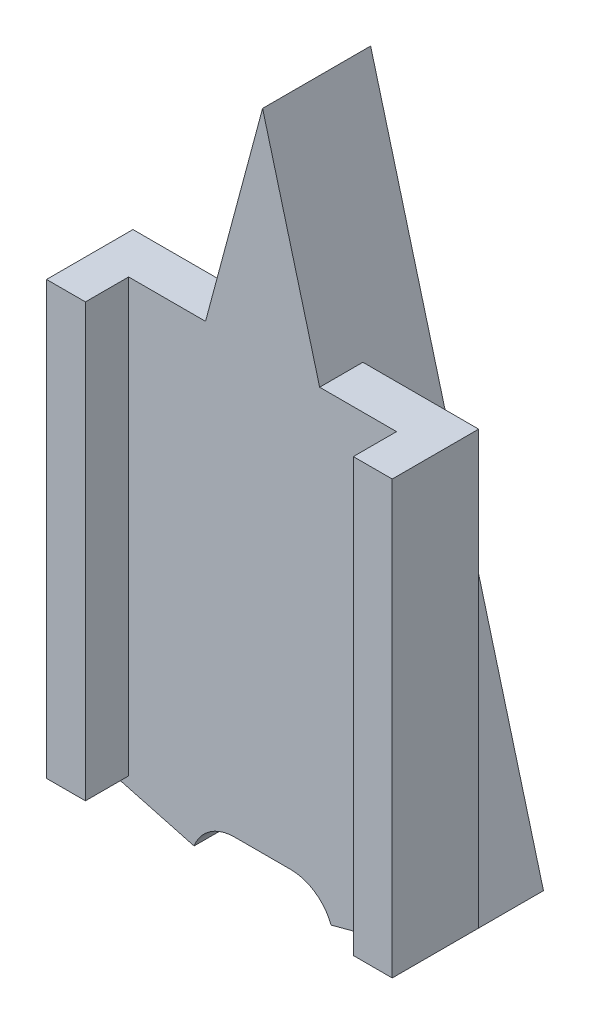
SolidWorks part; units mm, degrees
material "PA Type 6"
ref_plane "Ebene vorne" through (0, 0, 0) normal (0, 0, 1) x (1, 0, 0)
ref_plane "Ebene oben" through (0, 0, 0) normal (0, 1, 0) x (1, 0, 0)
ref_plane "Ebene rechts" through (0, 0, 0) normal (1, 0, 0) x (0, 0, -1)
sketch "Sketch1" plane through (0, 0, 0) normal (0, 0, 1) x (1, 0, 0)
  line L1 (0, 0) -> (8, 0)
  line L2 (0, 0) -> (0, -10)
  line L3 (0, -10) -> (8, -10)
  line L4 (8, 0) -> (8, -10)
extrude "Boss-Extrude1" add sketch "Sketch1" along normal blind 2
sketch "Sketch2" plane through (0, 0, 2) normal (0, 0, 1) x (1, 0, 0)
  line L0 (8, 0) -> (0, 0) construction
  line L1 (0.9, 0) -> (7.1, 0)
  line L2 (0.9, 0) -> (0.9, -10)
  line L3 (0.9, -10) -> (7.1, -10)
  line L4 (7.1, 0) -> (7.1, -10)
  line L5 (0, -10) -> (8, -10) construction
  line L6 (0, 0) -> (0, -10) construction
  line L7 (8, -10) -> (8, 0) construction
  dimension "D1" = 0.9
  dimension "D2" = 0.9
  dimension "D3" = 6.2
extrude "Cut-Extrude1" cut sketch "Sketch2" against normal blind 1
sketch "Sketch3" plane through (0, 0, 0) normal (0, 0, -1) x (-1, 0, 0)
  line L0 (-8, -10) -> (-4, 4.9282)
  line L1 (-8, -10) -> (-5.5852, -10.647)
  line L4 (-4, 0) -> (-4, -10) construction
  line L5 (-8, 0) -> (0, 0) construction
  line L6 (0, -10) -> (-8, -10) construction
  line L7 (-8, -5) -> (0, -5) construction
  line L8 (-8, -10) -> (-8, 0) construction
  line L9 (0, 0) -> (0, -10) construction
  line L10 (0, -10) -> (-4, 4.9282)
  line L11 (-4, -4.7311) -> (-5.5852, -10.647)
  line L12 (0, -10) -> (-2.4148, -10.647)
  line L13 (-2.4148, -10.647) -> (-4, -4.7311)
  dimension "D1" = 2.5
  dimension "D2" = 2.5
  dimension "D3" = 30
extrude "Boss-Extrude2" add sketch "Sketch3" along normal blind 1.5 and the other way blind 1
hole_wizard "M1x0.2 Tapped Hole1" positions "Sketch5" profile "Sketch4" tap size "M1x0.2" standard "DIN"
sketch "Sketch5" plane through (-2.5, -9.3301, 0) normal (-0.2588, -0.9659, 0) x (-0.9659, 0.2588, 0)
  line L0 (-3.8382, 1.5) -> (-3.8382, -1) construction
  line L1 (-5.0882, 1.5) -> (-2.5882, 1.5) construction
  line L2 (-5.0882, -1) -> (-2.5882, -1) construction
  line L4 (-5.0882, 0.25) -> (-2.5882, 0.25) construction
  line L5 (-5.0882, -1) -> (-5.0882, 1.5) construction
  line L6 (-2.5882, 0) -> (-2.5882, 1.5) construction
  point P0 (-5.116, 0.25)
sketch "Sketch4" plane through (2.4417, -10.6542, -0.25) normal (0, 0, 1) x (0.9659, -0.2588, 0)
  line L0 (0, 0) -> (0, 2.8403)
  line L1 (0, 2.8403) -> (0.4, 2.6)
  line L2 (0.4, 2.6) -> (0.4, 2)
  line L3 (0.4, 2) -> (0.5, 2)
  line L4 (0.5, 2) -> (0.5, 0)
  line L5 (0.5, 0) -> (0, 0)
  line L10 (0, 2.8403) -> (-0.4, 2.6) construction
  line L11 (0, -6.35) -> (0, 107.95) construction
  dimension "Tap Drill Dia." = 0.8
  dimension "Tap Drill Depth" = 2.6
  dimension "Thread Major Dia." = 1
  dimension "Thread Depth" = 2
  dimension "Drill Angle" = 118
hole_wizard "M1 Clearance Hole1" positions "Sketch6" profile "Sketch7" hole size "M1" standard "DIN"
sketch "Sketch6" plane through (3.0359, -11.3301, 0) normal (0.2588, -0.9659, 0) x (-0.9659, -0.2588, 0)
  point P0 (-2.3142, 0.25)
sketch "Sketch7" plane through (5.2712, -10.7312, -0.25) normal (0, 0, 1) x (0.9659, 0.2588, 0)
  line L0 (0, 0) -> (0, 5.3004)
  line L1 (0, 5.3004) -> (0.5, 5)
  line L2 (0.5, 5) -> (0.5, 0)
  line L5 (0.5, 0) -> (0, 0)
  line L10 (0, 5.3004) -> (-0.5, 5) construction
  line L11 (0, -6.35) -> (0, 107.95) construction
  dimension "Hole Dia." = 1
  dimension "Hole Depth" = 5
  dimension "Drill Angle" = 118
sketch "Sketch8" plane through (0, 0, -1.5) normal (0, 0, -1) x (-1, 0, 0)
  circle A0 centre (-4, -7.3) radius 0.4
extrude "Cut-Extrude2" cut sketch "Sketch8" against normal blind 1.5 rebuild error yes
fillet "Fillet2" radius 1 2 edges at (2.5882, -10, 0.6246) (5.4118, -10, 0.565)
